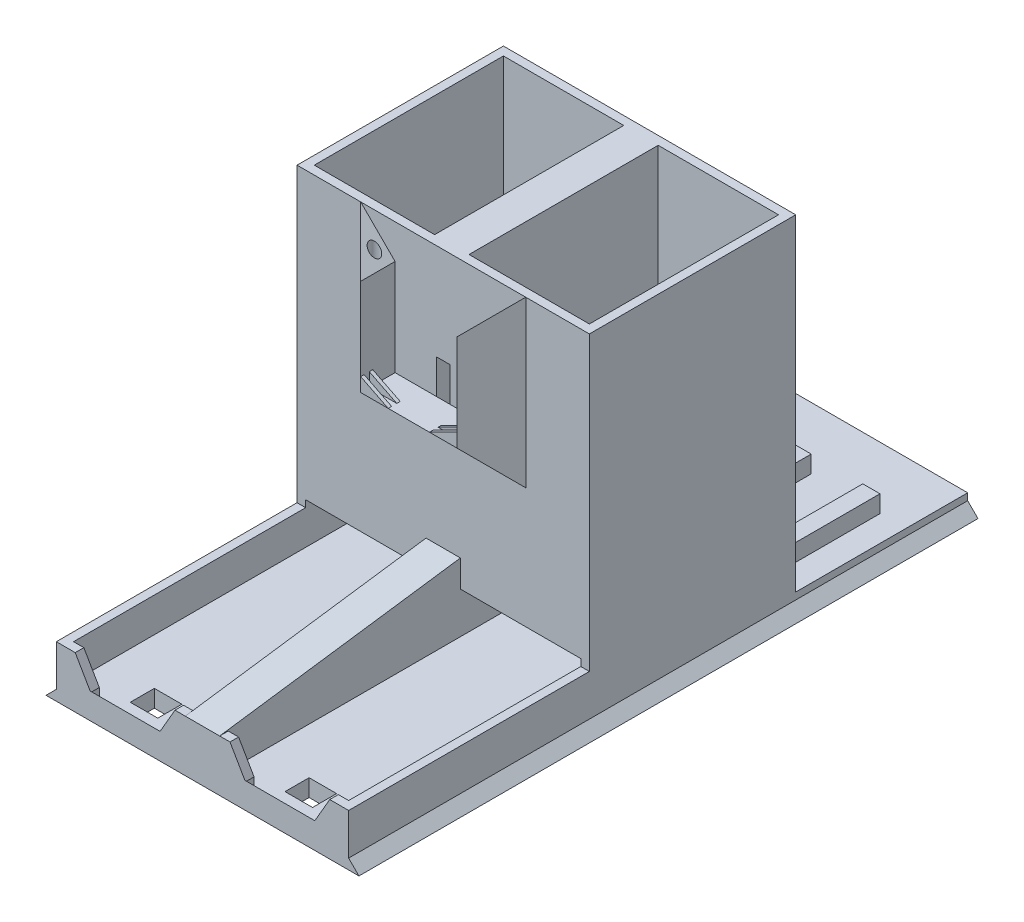
SolidWorks part; units mm, degrees
ref_plane "Front Plane" through (0, 0, 0) normal (0, 0, 1) x (1, 0, 0)
ref_plane "Top Plane" through (0, 0, 0) normal (0, 1, 0) x (1, 0, 0)
ref_plane "Right Plane" through (0, 0, 0) normal (1, 0, 0) x (0, 0, -1)
sketch "Sketch1" plane through (0, 0, 0) normal (0, 1, 0) x (1, 0, 0)
  line L1 (0, 0) -> (85, 0)
  line L2 (0, 0) -> (0, 60)
  line L3 (0, 60) -> (85, 60)
  line L4 (85, 0) -> (85, 60)
  dimension "D1" = 85
  dimension "D2" = 60
sketch "Sketch2" plane through (0, 0, 0) normal (0, 1, 0) x (1, 0, 0)
  line L1 (2.5, 57.5) -> (37.5, 57.5)
  line L2 (2.5, 57.5) -> (2.5, 2.5)
  line L3 (2.5, 2.5) -> (37.5, 2.5)
  line L4 (37.5, 57.5) -> (37.5, 2.5)
  line L5 (47.5, 57.5) -> (82.5, 57.5)
  line L6 (47.5, 57.5) -> (47.5, 2.5)
  line L7 (47.5, 2.5) -> (82.5, 2.5)
  line L8 (82.5, 57.5) -> (82.5, 2.5)
  dimension "D1" = 35
  dimension "D2" = 10
extrude "Boss-Extrude1" add sketch "Sketch1" along normal blind 100
extrude "Cut-Extrude1" cut sketch "Sketch2" along normal blind 95 from offset 5
sketch "Sketch3" plane through (0, 0, 0) normal (0, 0, 1) x (1, 0, 0)
  line L0 (85, 100) -> (85, 0) construction
  line L1 (0, 0) -> (85, 0)
  line L2 (0, 0) -> (0, 5)
  line L3 (0, 5) -> (85, 5)
  line L4 (85, 0) -> (85, 5)
extrude "Boss-Extrude2" add sketch "Sketch3" along normal blind 70
sketch "Sketch4" plane through (0, 5, 0) normal (0, 1, 0) x (1, 0, 0)
  line L0 (85, 0) -> (82.5, 0)
  line L5 (0, 0) -> (0, -70)
  line L18 (0, -70) -> (85, -70)
  line L19 (85, -70) -> (85, 0)
  line L20 (85, 0) -> (0, 0) construction
  line L21 (82.5, 0) -> (82.5, -67.5)
  line L22 (82.5, -67.5) -> (47.5, -67.5)
  line L23 (47.5, -67.5) -> (47.5, 0)
  line L24 (0, 0) -> (85, 0) construction
  line L25 (47.5, 0) -> (37.5, 0)
  line L26 (37.5, 0) -> (37.5, -67.5)
  line L27 (37.5, -67.5) -> (2.5, -67.5)
  line L28 (2.5, -67.5) -> (2.5, 0)
  line L29 (2.5, 0) -> (0, 0)
  dimension "D1" = 2.5
  dimension "D2" = 2.5
  dimension "D3" = 10
extrude "Boss-Extrude3" add sketch "Sketch4" along normal blind 10
sketch "Sketch5" plane through (0, 15, 0) normal (0, 1, 0) x (1, 0, 0)
  line L0 (37.5, -67.5) -> (2.5, -67.5) construction
  line L1 (10, -67.5) -> (30, -67.5)
  line L2 (10, -67.5) -> (10, -70)
  line L3 (10, -70) -> (30, -70)
  line L4 (30, -67.5) -> (30, -70)
  line L5 (0, -70) -> (85, -70) construction
  line L6 (82.5, -67.5) -> (47.5, -67.5) construction
  line L7 (75, -67.5) -> (55, -67.5)
  line L8 (75, -67.5) -> (75, -70)
  line L9 (75, -70) -> (55, -70)
  line L10 (55, -67.5) -> (55, -70)
  line L12 (37.5, 0) -> (37.5, -67.5) construction
  line L13 (47.5, -67.5) -> (47.5, 0) construction
  line L14 (82.5, 0) -> (82.5, -67.5) construction
  line L15 (2.5, -67.5) -> (2.5, 0) construction
  dimension "D1" = 7.5
  dimension "D2" = 7.5
  dimension "D3" = 7.5
  dimension "D4" = 7.5
extrude "Cut-Extrude2" cut sketch "Sketch5" against normal blind 7.5
sketch "Sketch6" plane through (0, 0, 0) normal (0, 0, 1) x (1, 0, 0)
  line L1 (2.5, 17) -> (37.5, 17)
  line L2 (2.5, 17) -> (2.5, 5)
  line L3 (2.5, 5) -> (37.5, 5)
  line L4 (37.5, 17) -> (37.5, 5)
  line L5 (47.5, 5) -> (82.5, 5)
  line L6 (47.5, 5) -> (47.5, 17)
  line L7 (47.5, 17) -> (82.5, 17)
  line L8 (82.5, 5) -> (82.5, 17)
  line L10 (0, 15) -> (0, 0) construction
  line L11 (85, 0) -> (85, 15) construction
  dimension "D1" = 2.5
  dimension "D2" = 10
  dimension "D3" = 2.5
extrude "Cut-Extrude4" cut sketch "Sketch6" against normal blind 57.5
sketch "Sketch7" plane through (0, 0, -60) normal (0, 0, -1) x (-1, 0, 0)
  line L0 (0, 15) -> (0, 0) construction
  line L1 (-85, 0) -> (-85, 15) construction
  circle A0 centre (-20, 11.5) radius 4
  circle A1 centre (-65, 11.5) radius 4
  dimension "D1" = 20
  dimension "D2" = 20
extrude "Cut-Extrude6" cut sketch "Sketch7" against normal up to next
sketch "Sketch9" plane through (0, 0, 0) normal (0, 1, 0) x (1, 0, 0)
  line L0 (85, 0) -> (85, 60) construction
  line L1 (0, 60) -> (85, 60)
  line L2 (0, 60) -> (0, 110)
  line L3 (0, 110) -> (85, 110)
  line L4 (85, 60) -> (85, 110)
  line L5 (0, 60) -> (0, 0) construction
extrude "Boss-Extrude4" add sketch "Sketch9" along normal blind 5
sketch "Sketch13" plane through (0, 5, 0) normal (0, 1, 0) x (1, 0, 0)
  line L1 (16, -64.5) -> (24, -64.5)
  line L2 (16, -64.5) -> (16, -57.5)
  line L3 (16, -57.5) -> (24, -57.5)
  line L4 (24, -64.5) -> (24, -57.5)
  line L5 (30, -67.5) -> (10, -67.5) construction
  line L10 (2.5, 57.5) -> (2.5, -67.5) construction
  line L11 (37.5, -67.5) -> (37.5, 57.5) construction
  line L12 (42.5, -70) -> (42.5, -52.9537) construction
  line L13 (30, -70) -> (55, -70) construction
  line L15 (61, -64.5) -> (61, -57.5)
  line L16 (69, -57.5) -> (61, -57.5)
  line L17 (69, -64.5) -> (69, -57.5)
  line L18 (69, -64.5) -> (61, -64.5)
  point P12 (16, -61)
  dimension "D1" = 13.5
  dimension "D2" = 13.5
  dimension "D3" = 7
  dimension "D4" = 3
extrude "Cut-Extrude8 (Button Holes)" cut sketch "Sketch13" against normal through all
sketch "Sketch14" plane through (0, 0, 0) normal (0, 0, 1) x (1, 0, 0)
  line L0 (0, 100) -> (0, 15) construction
  line L2 (18.5, 93.1727) -> (18.5, 52)
  line L4 (28.5, 90) -> (28.5, 62)
  line L5 (18.5, 52) -> (66.5, 52)
  line L7 (56.5, 90) -> (56.5, 62)
  line L9 (66.5, 93.1727) -> (66.5, 52)
  line L12 (28.5, 62) -> (56.5, 62)
  line L14 (28.5, 90) -> (56.5, 90)
  line L15 (18.5, 93.1727) -> (18.5, 100)
  line L16 (18.5, 100) -> (66.5, 100)
  line L17 (66.5, 93.1727) -> (66.5, 100)
  line L18 (0, 100) -> (85, 100) construction
  dimension "D1" = 10
  dimension "D2" = 10
  dimension "D3" = 10
  dimension "D4" = 28
  dimension "D5" = 10
  dimension "D6" = 28
  dimension "D7" = 18.5
extrude "Boss-Extrude5 (OLED Mount)" add sketch "Sketch14" along normal blind 10
sketch "Sketch40" plane through (0, 0, 10) normal (0, 0, 1) x (1, 0, 0)
  line L0 (28.5, 62) -> (36.5, 62)
  line L1 (28.5, 62) -> (56.5, 62) construction
  line L2 (36.5, 62) -> (28.5, 66)
  line L3 (28.5, 90) -> (28.5, 62) construction
  line L4 (28.5, 66) -> (28.5, 62)
  line L5 (56.5, 62) -> (48.5, 62)
  line L6 (48.5, 62) -> (56.5, 66)
  line L7 (56.5, 62) -> (56.5, 90) construction
  line L8 (56.5, 66) -> (56.5, 62)
  dimension "D1" = 8
  dimension "D2" = 4
  dimension "D3" = 8
  dimension "D4" = 4
extrude "Boss-Extrude6 (OLED Mount)" add sketch "Sketch40" against normal blind 1
extrude "Boss-Extrude7 (OLED Mount)" add sketch "Sketch40<2>" against normal blind 1 from offset 2.5 offset against normal yes
sketch "Sketch40<2>" plane through (0, 0, 10) normal (0, 0, 1) x (1, 0, 0) same geometry as "Sketch40"
chamfer "Chamfer2 (OLED Mount)" distance 10 angle 45 4 edges at (42.5, 52, 10) (66.5, 76, 10) (42.5, 100, 10) (18.5, 76, 10)
sketch "Sketch44" plane through (85, 0, 0) normal (1, 0, 0) x (0, 0, -1)
  line L0 (0, 62) -> (0, 72)
  line L1 (0, 100) -> (0, 15) construction
  line L3 (0, 72) -> (10.5, 62)
  line L4 (10.5, 62) -> (0, 62)
  dimension "D1" = 10.5
  dimension "D2" = 10
extrude "Cut-Extrude7 (OLED Cable Hole)" cut sketch "Sketch44" against normal blind 4 from offset 40.5 offset against normal yes
sketch "Sketch41" plane through (0, 0, 0) normal (0, 0, 1) x (1, 0, 0)
  line L0 (18.5, 100) -> (28.5, 90)
  line L1 (28.5, 90) -> (56.5, 90)
  line L2 (56.5, 90) -> (66.5, 100)
  line L3 (66.5, 100) -> (18.5, 100)
extrude "Cut-Extrude7 (Roof Cutout)" cut sketch "Sketch41" along normal through all
sketch "Sketch18" plane through (0, 62, 0) normal (0, 1, 0) x (1, 0, 0)
  line L5 (47.5, 57.5) -> (47.5, -67.5) construction
  line L6 (47.5, 2.5) -> (82.5, 2.5) construction
  line L8 (40.5, 10.5) -> (44.5, 10.5)
  line L9 (40.5, 10.5) -> (40.5, 2.5)
  line L10 (40.5, 2.5) -> (44.5, 2.5)
  line L11 (44.5, 10.5) -> (44.5, 2.5)
  line L12 (37.5, -67.5) -> (37.5, 57.5) construction
  dimension "D1" = 3
  dimension "D2" = 3
  dimension "D3" = 8
extrude "Cut-Extrude9 (OLED Cable)" cut sketch "Sketch18" against normal through all
chamfer "Chamfer6 (OLED Cable Hole)" distance 2.5 angle 60 1 edges at (42.5, 62, -2.5) first distance on face at (42.5, 62, 5.35)
sketch "Sketch45" plane through (0, 100, 0) normal (0, 1, 0) x (1, 0, 0)
  line L0 (18.5, 0) -> (66.5, 0) construction
  line L1 (28.5, -6.5) -> (28.5, 0) construction
  line L3 (42.5, 0) -> (42.5, -4.4125) construction
  circle A1 centre (25.5, -3) radius 1.5
  circle A2 centre (59.5, -3) radius 1.5
  dimension "D1" = 3
  dimension "D2" = 3
extrude "Cut-Extrude7 (Roof Holes)" cut sketch "Sketch45" against normal blind 15
sketch "Sketch20" plane through (0, 5, 0) normal (0, 1, 0) x (1, 0, 0)
  line L0 (0, 60) -> (85, 60) construction
  line L1 (70, 60) -> (60, 60)
  line L2 (70, 60) -> (70, 70)
  line L3 (70, 70) -> (60, 70)
  line L4 (60, 60) -> (60, 70)
  line L5 (85, 60) -> (85, 110) construction
  line L7 (42.5, 110) -> (42.5, 60) construction
  line L8 (85, 110) -> (0, 110) construction
  line L9 (15, 70) -> (25, 70)
  line L10 (25, 60) -> (25, 70)
  line L11 (15, 60) -> (25, 60)
  line L12 (15, 60) -> (15, 70)
  point P8 (65, 60)
  dimension "D1" = 10
  dimension "D2" = 15
  dimension "D3" = 10
  dimension "D4" = 42.5
extrude "Cut-Extrude10 (Solenoid Wire Hole)" cut sketch "Sketch20" against normal through all
sketch "Sketch21" plane through (0, 5, 0) normal (0, 1, 0) x (1, 0, 0)
  line L0 (70, 60) -> (85, 60) construction
  line L1 (72.5, 60) -> (77.5, 60)
  line L2 (72.5, 60) -> (72.5, 92)
  line L3 (72.5, 92) -> (77.5, 92)
  line L4 (77.5, 60) -> (77.5, 92)
  line L7 (85, 110) -> (0, 110) construction
  line L9 (42.5, 60) -> (42.5, 110) construction
  line L10 (25, 60) -> (60, 60) construction
  line L11 (0, 110) -> (0, 60) construction
  line L12 (65, 110) -> (65, 60) construction
  line L13 (85, 60) -> (85, 110) construction
  line L15 (52.5, 60) -> (52.5, 92)
  line L16 (57.5, 92) -> (52.5, 92)
  line L17 (57.5, 60) -> (57.5, 92)
  line L18 (57.5, 60) -> (52.5, 60)
  line L19 (27.5, 60) -> (32.5, 60)
  line L20 (27.5, 60) -> (27.5, 92)
  line L21 (32.5, 60) -> (32.5, 92)
  line L22 (27.5, 92) -> (32.5, 92)
  line L23 (7.5, 60) -> (7.5, 92)
  line L24 (12.5, 92) -> (7.5, 92)
  line L25 (12.5, 60) -> (12.5, 92)
  line L26 (12.5, 60) -> (7.5, 60)
  dimension "D1" = 5
  dimension "D2" = 42.5
  dimension "D3" = 20
  dimension "D4" = 7.5
  dimension "D5" = 32
extrude "Boss-Extrude9 (Solenoid Side Support)" add sketch "Sketch21" along normal blind 5
chamfer "Chamfer3 (Thumb)" distance 2.5 angle 45 2 edges at (20, 7.5, 67.5) (65, 7.5, 67.5)
chamfer "Chamfer5 (Thumb)" distance 4.5 angle 60 4 edges at (75, 15, 68.75) (55, 15, 68.75) (30, 15, 68.75) (10, 15, 68.75) first distance on face at (80.8333, 15, 45.8333) first distance on face at (42.5, 15, 51.25) first distance on face at (4.1667, 15, 45.8333)
sketch "Sketch37" plane through (0, 0, 70) normal (0, 0, 1) x (1, 0, 0)
  line L0 (85, 0) -> (88, 0)
  line L1 (88, 0) -> (85, 3)
  line L2 (85, 0) -> (85, 15) construction
  line L3 (85, 3) -> (85, 0)
  line L4 (0, 0) -> (-3, 0)
  line L5 (-3, 0) -> (0, 3)
  line L6 (0, 15) -> (0, 0) construction
  line L7 (0, 3) -> (0, 0)
  dimension "D1" = 3
  dimension "D2" = 3
  dimension "D3" = 3
  dimension "D4" = 3
extrude "Boss-Extrude5 (Guide)" add sketch "Sketch37" against normal through all
sketch "Sketch42" plane through (0, 15, 0) normal (0, 1, 0) x (1, 0, 0)
  line L1 (37.5, 0) -> (47.5, 0)
  line L2 (37.5, 0) -> (37.5, -70)
  line L3 (37.5, -70) -> (47.5, -70)
  line L4 (47.5, 0) -> (47.5, -70)
  line L16 (34.5, -70) -> (50.5, -70) construction
extrude "Boss-Extrude8" add sketch "Sketch42" along normal blind 10
chamfer "Chamfer5" distance 10 angle 82 1 edges at (42.5, 25, 70) first distance on face at (42.5, 11.4444, 70)
